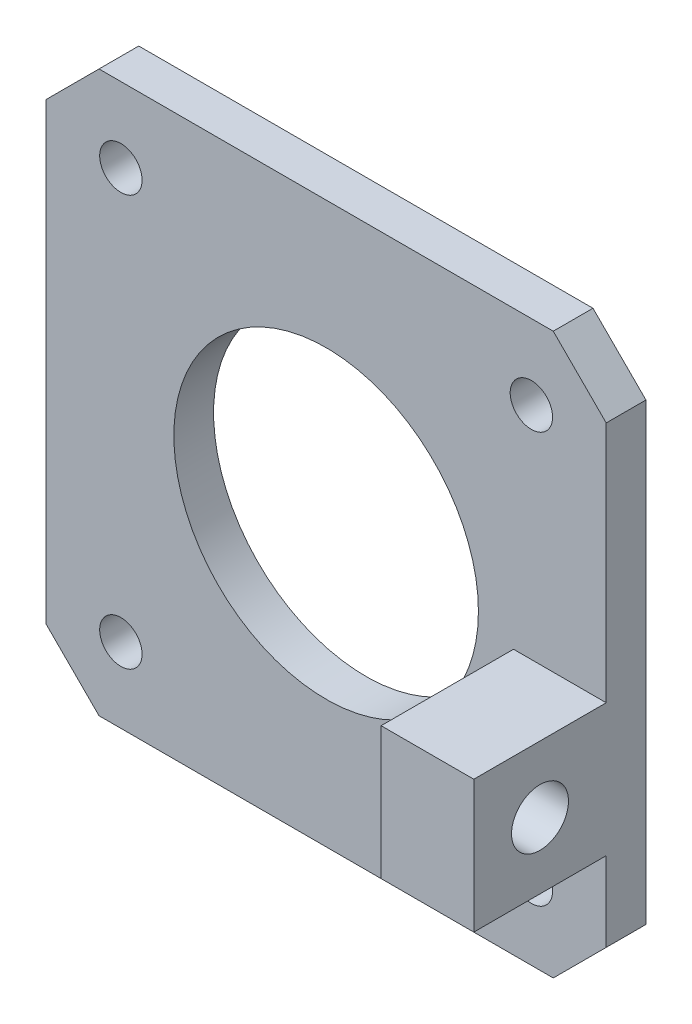
SolidWorks part; units mm, degrees
ref_plane "Front Plane" through (0, 0, 0) normal (0, 0, 1) x (1, 0, 0)
ref_plane "Top Plane" through (0, 0, 0) normal (0, 1, 0) x (1, 0, 0)
ref_plane "Right Plane" through (0, 0, 0) normal (1, 0, 0) x (0, 0, -1)
sketch "Croquis1" plane through (0, 0, 0) normal (0, 0, 1) x (1, 0, 0)
  line L0 (-21.15, 17.15) -> (-17.15, 21.15) construction
  line L1 (-21.15, -17.15) -> (-21.15, 17.15) construction
  line L2 (-17.15, -21.15) -> (-21.15, -17.15) construction
  line L3 (17.15, -21.15) -> (-17.15, -21.15) construction
  line L4 (17.15, 21.15) -> (16.7358, 20.15)
  line L5 (16.7358, 20.15) -> (20.15, 16.7358)
  line L6 (20.15, 16.7358) -> (21.15, 17.15)
  line L7 (21.15, 17.15) -> (17.15, 21.15)
  line L11 (21.15, 17.15) -> (17.15, 21.15)
  line L12 (21.15, -17.15) -> (17.15, -21.15) construction
  line L13 (21.15, 17.15) -> (21.15, -17.15) construction
  line L14 (-17.15, 21.15) -> (17.15, 21.15) construction
  line L15 (-21.15, 17.15) -> (-17.15, 21.15)
  line L16 (-21.15, -17.15) -> (-21.15, 17.15)
  line L17 (-17.15, -21.15) -> (-21.15, -17.15)
  line L18 (17.15, -21.15) -> (-17.15, -21.15)
  line L19 (21.15, -17.15) -> (17.15, -21.15)
  line L20 (21.15, 17.15) -> (21.15, -17.15)
  line L21 (-17.15, 21.15) -> (17.15, 21.15)
  circle A2 centre (-15.5, 15.5) radius 1.6
  circle A3 centre (-15.5, 15.5) radius 1.6
  circle A5 centre (-15.5, -15.5) radius 1.6
  circle A6 centre (-15.5, -15.5) radius 1.6
  circle A8 centre (15.5, 15.5) radius 1.6
  circle A9 centre (15.5, 15.5) radius 1.6
  circle A10 centre (0, 0) radius 11.5 construction
  circle A11 centre (15.5, -15.5) radius 1.6
  circle A12 centre (15.5, -15.5) radius 1.6
  circle A13 centre (0, 0) radius 11.5
  dimension "D1" = 0
  dimension "D2" = 0.35
  dimension "D3" = 0.35
  dimension "D4" = 0.35
  dimension "D5" = 0.35
extrude "Saliente-Extruir1" add sketch "Croquis1" along normal blind 3
sketch "Croquis2" plane through (21.15, 0, 0) normal (1, 0, 0) x (0, 0, -1)
  line L0 (-331, -6.05) -> (-331, -6.25) construction
  line L1 (-331, -6.05) -> (-331, -6.25)
  line L2 (-331, -6.15) -> (216.1427, -6.15) construction
  line L3 (-3, -17.15) -> (-3, 17.15) construction
  line L4 (-13, -11.15) -> (-3, -11.15)
  line L5 (-13, -11.15) -> (-13, -1.15)
  line L6 (-13, -1.15) -> (-3, -1.15)
  line L7 (-3, -11.15) -> (-3, -1.15)
  line L8 (-8, -1.15) -> (-8, -11.15) construction
  line L9 (-13, -6.15) -> (-3, -6.15) construction
  circle A0 centre (-8, -6.15) radius 2.15
  point P2 (-331, -6.15)
  point P5 (-8, -6.15)
  line M5 (-3, 17.15) -> (-3, -17.15)
  dimension "D3" = 4.3
  dimension "D1" = 10
  dimension "D2" = 10
extrude "Saliente-Extruir2" add sketch "Croquis2" against normal blind 7 contours L6 L5 L4 A0 M5 region at (21.15, -6.15, 12.8586)
